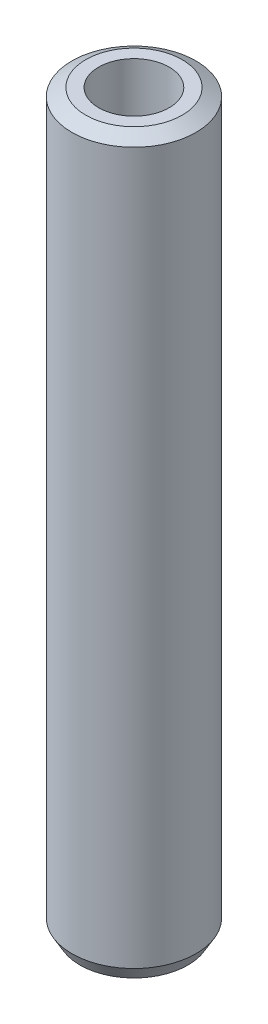
SolidWorks part; units mm, degrees
ref_plane "Front Plane" through (0, 0, 0) normal (0, 0, 1) x (1, 0, 0)
ref_plane "Top Plane" through (0, 0, 0) normal (0, 1, 0) x (1, 0, 0)
ref_plane "Right Plane" through (0, 0, 0) normal (1, 0, 0) x (0, 0, -1)
sketch "Sketch1" plane through (0, 0, 0) normal (0, 1, 0) x (1, 0, 0)
  circle A0 centre (0, 0) radius 32.5
  dimension "SHAFT_OD" = 65
extrude "Boss-Extrude1" add sketch "Sketch1" along normal blind 384.0834
sketch "Sketch2" plane through (0, 0, 0) normal (0, 1, 0) x (1, 0, 0)
  circle A0 centre (0, 0) radius 18.4758
  dimension "BORE_D" = 36.9517
extrude "Cut-Extrude1" cut sketch "Sketch2" along normal through all
chamfer "Chamfer1" distance 4.1932 angle 60 2 edges at (0, 384.0834, 32.5) (0, 0, 32.5) first distance on face at (0, 384.0834, 32.5) first distance on face at (0, 0, 18.4758)
